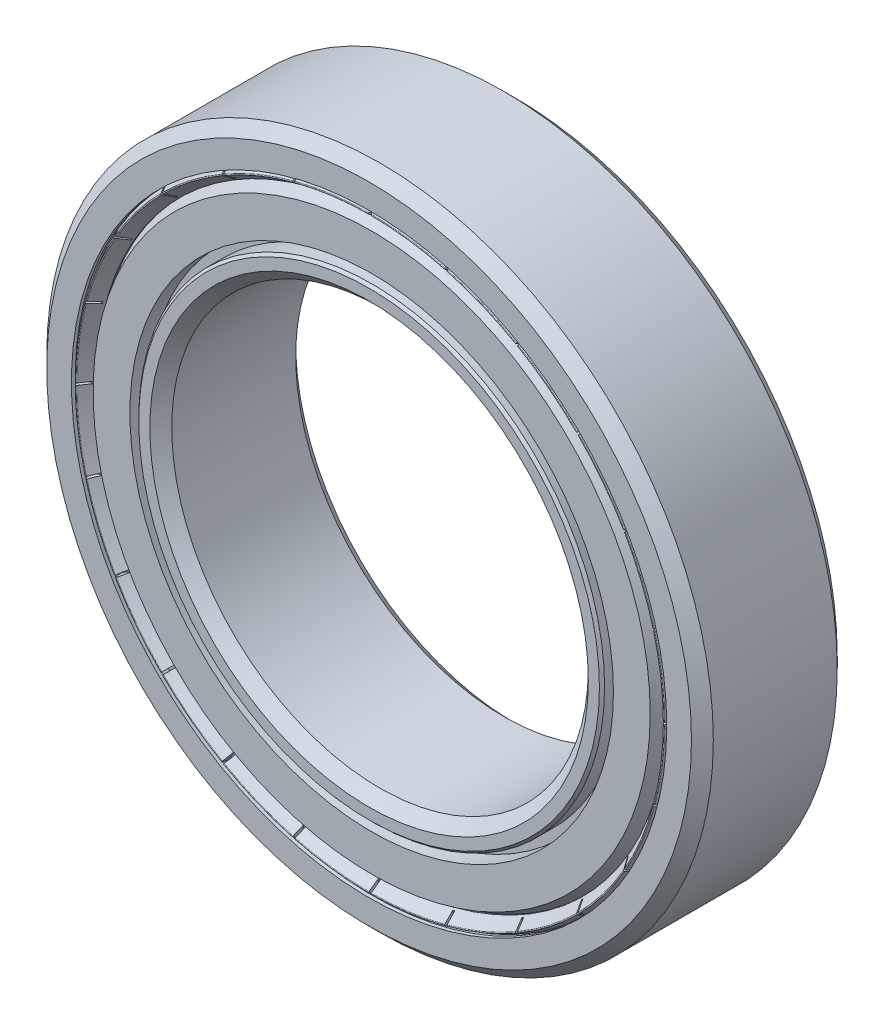
SolidWorks part; units mm, degrees
ref_plane "Front Plane" through (0, 0, 0) normal (0, 0, 1) x (1, 0, 0)
ref_plane "Top Plane" through (0, 0, 0) normal (0, 1, 0) x (1, 0, 0)
ref_plane "Right Plane" through (0, 0, 0) normal (1, 0, 0) x (0, 0, -1)
sketch "Sketch1" plane through (0, 0, 0) normal (0, 0, 1) x (1, 0, 0)
  circle A0 centre (0, 0) radius 10
  circle A1 centre (0, 0) radius 16
  dimension "OD" = 32
  dimension "ID" = 20
sketch "Sketch2" plane through (0, 0, 0) normal (1, 0, 0) x (0, 0, -1)
  line L0 (-3.5, 16) -> (3.5, 16)
  line L1 (-3.5, 10) -> (-3.5, -10) construction
  line L2 (3.5, 16) -> (3.5, -16) construction
  line L3 (-3.5, 0) -> (3.5, 0) construction
  line L6 (0, 16) -> (0, 10) construction
  circle A0 centre (0, 13) radius 2.1 construction
  point P8 (0, 16)
  dimension "Approx. Ball Dia." = 4.2
  dimension "Width" = 7
  dimension "For Shaft Diameter" = 20
  dimension "For Housing ID" = 32
sketch "Sketch3" plane through (0, 0, 0) normal (1, 0, 0) x (0, 0, -1)
  line L0 (0, 0) -> (0, 20) construction
  line L1 (-3.5, 10) -> (-3.5, -10) construction
  line L2 (2.975, 16) -> (-2.975, 16)
  line L3 (-2.975, 16) -> (-3.5, 15.475)
  line L4 (-3.5, 15.475) -> (-3.5, 14.2898)
  line L5 (-3.5, 14.2898) -> (-3.325, 14.2898)
  line L6 (-3.325, 14.2898) -> (-3.325, 14.6949)
  line L7 (-3.325, 14.6949) -> (-3.2013, 14.8187)
  line L8 (-3.2013, 14.8187) -> (-1.05, 14.8187)
  line L10 (-3.5, 16) -> (3.5, 16) construction
  line L12 (-3.325, 14.6949) -> (-3.325, 15.1) construction
  line L13 (3.2013, 14.8187) -> (1.05, 14.8187)
  line L14 (3.325, 14.6949) -> (3.2013, 14.8187)
  line L15 (3.325, 14.2898) -> (3.325, 14.6949)
  line L16 (3.5, 14.2898) -> (3.325, 14.2898)
  line L17 (3.5, 15.475) -> (3.5, 14.2898)
  line L18 (2.975, 16) -> (3.5, 15.475)
  line L19 (2.975, 10) -> (-2.975, 10)
  line L20 (-2.975, 10) -> (-3.5, 10.525)
  line L21 (-3.5, 10.525) -> (-3.5, 11.0576)
  line L22 (-3.5, 11.0576) -> (-3.3763, 11.1813)
  line L23 (-3.3763, 11.1813) -> (-1.05, 11.1813)
  line L25 (3.3763, 11.1813) -> (1.05, 11.1813)
  line L26 (3.5, 11.0576) -> (3.3763, 11.1813)
  line L27 (3.5, 10.525) -> (3.5, 11.0576)
  line L28 (2.975, 10) -> (3.5, 10.525)
  circle A2 centre (0, 13) radius 2.1 construction
  arc A3 (-1.05, 14.8187) -> (1.05, 14.8187) centre (0, 13) cw
  arc A4 (-1.05, 11.1813) -> (1.05, 11.1813) centre (0, 13) ccw
  point P5 (0, 15.1)
  point P31 (0, 16)
  point P37 (0, 10)
  dimension "D1" = 45
  dimension "D2" = 0.175
  dimension "D3" = 2.1
  dimension "D4" = 0.525
revolve "Revolve1" add sketch "Sketch3" angle 360 about L3
sketch "Sketch4" plane through (0, 0, 0) normal (1, 0, 0) x (0, 0, -1)
  line L0 (0, 15.1) -> (0, 10.9)
  line L1 (0, 16) -> (0, 10) construction
  circle A0 centre (0, 13) radius 2.1 construction
  arc A1 (0, 10.9) -> (0, 15.1) centre (0, 13) cw
revolve "Revolve2" add sketch "Sketch4" angle 360 about L6
pattern_circular "CirPattern1" count 12 over 360 about axis through (0, 0, 3.5) along (0, 0, -1) of bodies 106
sketch "Sketch5" plane through (0, 0, 0) normal (1, 0, 0) x (0, 0, -1)
  line L0 (-2.1, 13) -> (-2.1, 11.1813) construction
  line L1 (-3.3763, 11.1813) -> (-1.05, 11.1813) construction
  line L3 (-2.1, 11.1813) -> (-2.5254, 11.1813)
  line L4 (-2.5254, 11.1813) -> (-2.5254, 11.6068)
  line L5 (-2.5254, 11.6068) -> (-3.3763, 11.6068)
  line L6 (-3.3763, 11.6068) -> (-3.3763, 13.3732)
  line L7 (-3.3763, 13.3732) -> (-2.5254, 13.8644)
  line L8 (-2.5254, 13.8644) -> (-2.1, 13.8644)
  line L9 (-2.1, 13.8644) -> (-2.1, 11.1813)
  line L10 (0, 13) -> (0, 16) construction
  line L11 (2.5254, 13.8644) -> (2.1, 13.8644)
  line L12 (3.3763, 13.3732) -> (2.5254, 13.8644)
  line L13 (3.3763, 11.6068) -> (3.3763, 13.3732)
  line L14 (2.5254, 11.6068) -> (3.3763, 11.6068)
  line L15 (2.5254, 11.1813) -> (2.5254, 11.6068)
  line L16 (2.1, 11.1813) -> (2.5254, 11.1813)
  line L17 (2.1, 13.8644) -> (2.1, 11.1813)
  line L18 (-3.3763, 13.3732) -> (-2.9508, 13.3732) construction
  line L19 (-2.9508, 13.3732) -> (-2.5254, 13.3732) construction
  line L20 (-2.5254, 13.3732) -> (-2.1, 13.3732) construction
  line L21 (-2.5254, 13.8644) -> (-2.5254, 14.2898) construction
  circle A0 centre (0, 13) radius 2.1 construction
  dimension "D1" = 30
revolve "Revolve3" add sketch "Sketch5" angle 360 about L3
sketch "Sketch6" plane through (0, 0, 0) normal (1, 0, 0) x (0, 0, -1)
  line L0 (-2.7978, 14.2898) -> (-3.1937, 14.2898)
  line L1 (-3.1937, 14.2898) -> (-3.5, 14.113)
  line L2 (-3.5, 14.113) -> (-2.9028, 13.6948)
  line L4 (-3.3763, 13.3732) -> (-2.5254, 13.8644) construction
  line L5 (-2.7978, 13.7072) -> (-2.7978, 14.2898)
  line L6 (-3.5, 14.2898) -> (-3.325, 14.2898) construction
  line L7 (-2.9028, 13.6948) -> (-2.8678, 13.6948)
  line L8 (-2.8678, 13.6948) -> (-2.7978, 13.7072)
  line L9 (-3.5, 15.475) -> (-3.5, -15.475) construction
  line L11 (-2.8678, 13.6948) -> (-2.8328, 13.6948) construction
  line L12 (-2.8328, 13.6948) -> (-2.7978, 13.6948) construction
  point P27 (-2.9958, 14.2898)
  dimension "D1" = 30
  dimension "D3" = 10
  dimension "D2" = 35
  dimension "D4" = 0.035
  dimension "D5" = 0.3062
revolve "Revolve4" add sketch "Sketch6" angle 360 about L3
fillet "Fillet1" radius 0.035 1 edges at (14.113, 0, 3.5)
sketch "Sketch7" plane through (0, 0, 0) normal (0, 0, 1) x (1, 0, 0)
  line L0 (-0.05, 14.2898) -> (-0.05, 14.3898)
  line L1 (-0.05, 14.2898) -> (0.05, 14.2898) construction
  line L2 (-0.05, 14.2898) -> (-0.05, 13.6948)
  line L3 (-0.05, 13.6948) -> (0.05, 13.6948) construction
  line L4 (0.05, 14.2898) -> (0.05, 13.6948)
  line L5 (-0.05, 14.3898) -> (0.05, 14.3898)
  line L6 (0.05, 14.3898) -> (0.05, 14.2898)
  line L7 (-0.05, 13.6948) -> (-0.05, 13.5948)
  line L8 (-0.05, 13.5948) -> (0.05, 13.5948)
  line L9 (0.05, 13.5948) -> (0.05, 13.6948)
  dimension "D1" = 0.1
extrude "Cut-Extrude1" cut sketch "Sketch7" along normal through all from vertex starting at point (0, 14.2898, 2.9958)
pattern_circular "CirPattern2" count 24 over 360 about axis through (0, 0, 3.5) along (0, 0, -1) of "Cut-Extrude1"
mirror "Mirror1" about plane through (0, 0, 0) normal (0, 0, 1) of bodies 120
equation "\"Approx. Ball Dia.@Sketch2\"=( \"OD@Sketch1\" - \"ID@Sketch1\" )  * .5 * .7"
equation "\"D2@Sketch3\"=\"Width@Sketch2\"*.025"
equation "\"D3@Sketch3\"=\"Approx. Ball Dia.@Sketch2\"*.5"
equation "\"D4@Sketch3\"=\"Width@Sketch2\"*.075"
equation "\"Approx No of Balls\"= ( pi * \"OD@Sketch1\" ) * .5 / \"Approx. Ball Dia.@Sketch2\""
equation "\"D1@CirPattern1\"=\"Approx No of Balls\""
equation "\"D4@Sketch6\"=\"D2@Sketch3\"*.2"
equation "\"D1@CirPattern2\"=\"Approx No of Balls\"*2"
equation "\"D5@Sketch6\"=\"D2@Sketch3\"*1.75"
equation "\"D1@Fillet1\"=\"d4@sketch6\""
